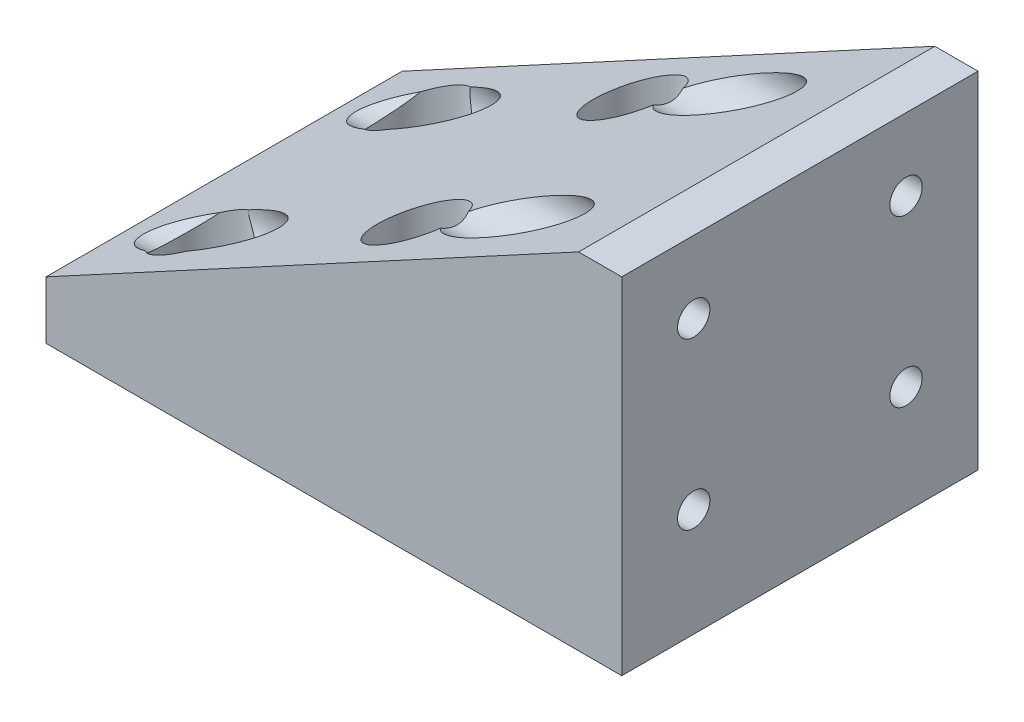
SolidWorks part; units mm, degrees
ref_plane "Front Plane" through (0, 0, 0) normal (0, 0, 1) x (1, 0, 0)
ref_plane "Top Plane" through (0, 0, 0) normal (0, 1, 0) x (1, 0, 0)
ref_plane "Right Plane" through (0, 0, 0) normal (1, 0, 0) x (0, 0, -1)
sketch "Sketch1" plane through (0, 0, 0) normal (0, 1, 0) x (1, 0, 0)
  line L1 (-40, -24.75) -> (40, -24.75)
  line L2 (-40, -24.75) -> (-40, 24.75)
  line L3 (-40, 24.75) -> (40, 24.75)
  line L4 (40, -24.75) -> (40, 24.75)
  line L5 (-40, -24.75) -> (40, 24.75) construction
  line L6 (-40, 24.75) -> (40, -24.75) construction
  point P0 (0, 0)
  point P6 (-28.25, 15)
  point P7 (-28.25, -15)
  point P8 (1.75, 15)
  point P9 (1.75, -15)
  point P10 (0, 0)
  point P11 (0, 0)
  point P12 (0, 0)
  point P13 (0, 0)
  dimension "D1" = 49.5
  dimension "D2" = 80
  dimension "D3" = 38.25
  dimension "D4" = 30
  dimension "D5" = 15
  dimension "D6" = 30
extrude "Boss-Extrude1" add sketch "Sketch1" against normal blind 8 and the other way blind 40
chamfer "Chamfer1" distance 40 distance2 74 1 edges at (-40, 40, 0) first distance on face at (-40, 16, 0)
hole_wizard "CSK for M4 SFHCS1" positions "Sketch2" profile "Sketch3" countersink size "M4" standard "ANSI Metric" end condition through all
sketch "Sketch2" plane through (0, 0, 0) normal (0, 1, 0) x (1, 0, 0)
  point P0 (-28.25, 15)
  point P3 (1.75, 15)
  point P6 (1.75, -15)
  point P9 (-28.25, -15)
sketch "Sketch3" plane through (-28.25, 0, -15) normal (1, 0, 0) x (0, 0, 1)
  line L0 (0, 0) -> (0, 8)
  line L1 (0, 8) -> (2.25, 8)
  line L2 (2.25, 8) -> (2.25, 3.23)
  line L3 (2.25, 3.23) -> (5.48, 0)
  line L5 (5.48, 0) -> (0, 0)
  line L6 (-2.25, 3.23) -> (-5.48, 0) construction
  line L11 (0, -6.35) -> (0, 107.95) construction
  dimension "Thru Hole Dia." = 4.5
  dimension "Thru Hole Depth" = 8
  dimension "Near C'Sink Dia." = 10.96
  dimension "Near C'Sink Angle" = 90
sketch "Sketch4" plane through (0, 0, 0) normal (0, -1, 0) x (1, 0, 0)
  circle A0 centre (1.75, -15) radius 5.48 construction
  circle A1 centre (-28.25, -15) radius 5.48
  circle A2 centre (-28.25, -15) radius 5.48
  circle A3 centre (1.75, 15) radius 5.48 construction
  circle A4 centre (-28.25, 15) radius 5.48 construction
  circle A5 centre (1.75, -15) radius 5.48
  circle A6 centre (1.75, 15) radius 5.48
  circle A7 centre (-28.25, 15) radius 5.48
  dimension "D1" = 0
extrude "Cut-Extrude1" cut sketch "Sketch4" against normal through all
ref_plane "Plane1" through (34, 0, 0) normal (1, 0, 0) x (0, 0, -1)
ref_plane "Plane2" through (33, 0, 0) normal (1, 0, 0) x (0, 0, -1)
hole_wizard "CSK for #8 Flat Head Machine Screw1" positions "Sketch5" profile "Sketch6" countersink size "#8" standard "ANSI Inch" end condition through all
sketch "Sketch5" plane through (33, 0, 0) normal (1, 0, 0) x (0, 0, -1)
  line L0 (-24.75, 40) -> (24.75, 40) construction
  line L1 (-24.75, 40) -> (-24.75, -8) construction
  line L2 (-24.75, -8) -> (24.75, -8) construction
  line L3 (24.75, 40) -> (24.75, -8) construction
  point P0 (-14.75, 30)
  point P2 (14.75, 30)
  point P4 (14.75, 7)
  point P6 (-14.75, 7)
  point P13 (0, 0)
  point P14 (0, 0)
  point P15 (0, 0)
  point P16 (0, 0)
  dimension "D1" = 10
  dimension "D2" = 10
  dimension "D3" = 15
  dimension "D4" = 10
sketch "Sketch6" plane through (33, 30, 14.75) normal (0, 1, 0) x (0, 0, 1)
  line L0 (0, 0) -> (0, 7)
  line L1 (0, 7) -> (2.2479, 7)
  line L2 (2.2479, 7) -> (2.2479, 3.2645)
  line L3 (2.2479, 3.2645) -> (5.0857, 0)
  line L5 (5.0857, 0) -> (0, 0)
  line L6 (-2.2479, 3.2645) -> (-5.0857, 0) construction
  line L11 (0, -6.35) -> (0, 107.95) construction
  dimension "Thru Hole Dia." = 4.4958
  dimension "Thru Hole Depth" = 7
  dimension "Near C'Sink Dia." = 10.1714
  dimension "Near C'Sink Angle" = 82
sketch "Sketch7" plane through (33, 0, 0) normal (1, 0, 0) x (0, 0, -1)
  circle A0 centre (-14.75, 7) radius 5.0857 construction
  circle A1 centre (14.75, 7) radius 5.0857 construction
  circle A2 centre (14.75, 30) radius 5.0857 construction
  circle A3 centre (-14.75, 30) radius 5.0857 construction
  circle A4 centre (-14.75, 7) radius 5.0857
  circle A5 centre (14.75, 7) radius 5.0857
  circle A6 centre (14.75, 30) radius 5.0857
  circle A7 centre (-14.75, 30) radius 5.0857
extrude "Cut-Extrude2" cut sketch "Sketch7" against normal through all
